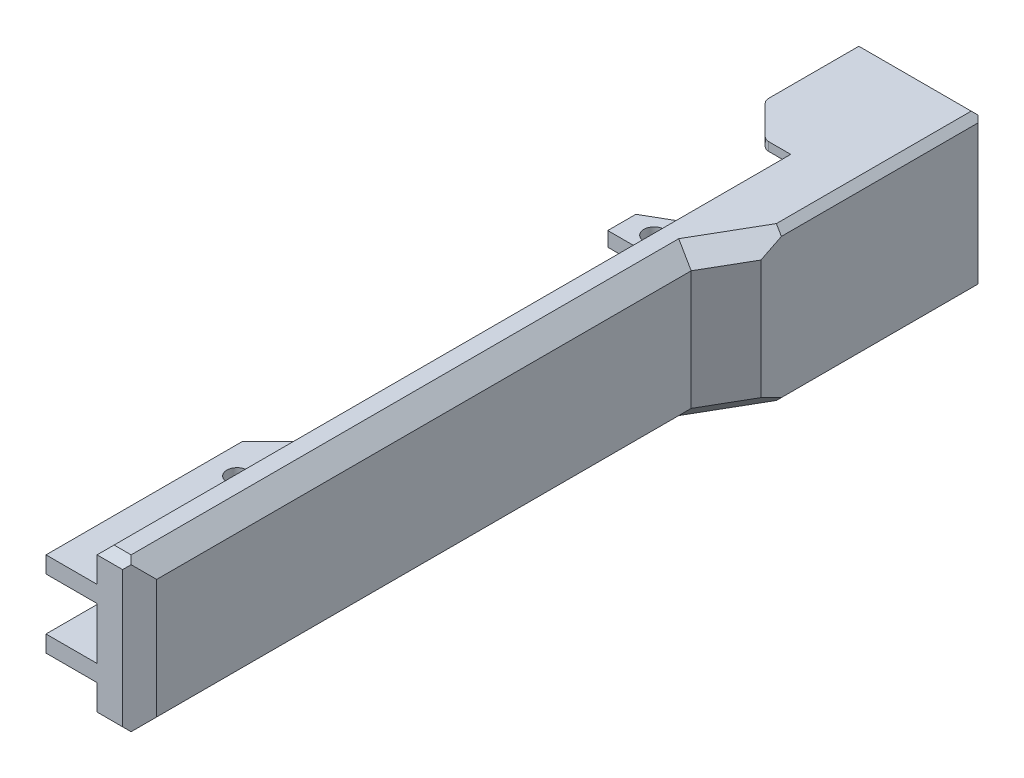
SolidWorks part; units mm, degrees
ref_plane "前视基准面" through (0, 0, 0) normal (0, 0, 1) x (1, 0, 0)
ref_plane "上视基准面" through (0, 0, 0) normal (0, 1, 0) x (1, 0, 0)
ref_plane "右视基准面" through (0, 0, 0) normal (1, 0, 0) x (0, 0, -1)
sketch "草图2" plane through (0, 0, 0) normal (1, 0, 0) x (0, 0, -1)
  line L0 (-24.1958, 9) -> (135.844, 9) construction
  line L1 (0, 0) -> (96.5, 0)
  line L2 (0, 0) -> (0, 18)
  line L3 (0, 18) -> (96.5, 18)
  line L4 (96.5, 0) -> (96.5, 18)
  dimension "D1" = 18
  dimension "D2" = 96.5
extrude "凸台-拉伸1" add sketch "草图2" along normal blind 14
sketch "草图6" plane through (0, 0, -96.5) normal (0, 0, -1) x (-1, 0, 0)
  line L0 (0, 0) -> (0, 18) construction
  line L1 (0, 12.05) -> (-6, 12.05)
  line L2 (0, 12.05) -> (0, 5.95)
  line L3 (0, 5.95) -> (-6, 5.95)
  line L4 (-6, 12.05) -> (-6, 5.95)
  line L5 (5.6103, 9) -> (-10.6258, 9) construction
  line L6 (0, 18) -> (-6, 18)
  line L7 (0, 18) -> (0, 14)
  line L8 (0, 14) -> (-6, 14)
  line L9 (-6, 18) -> (-6, 14)
  line L10 (0, 0) -> (-6, 0)
  line L11 (0, 0) -> (0, 4)
  line L12 (0, 4) -> (-6, 4)
  line L13 (-6, 0) -> (-6, 4)
  line M13 (0, 0) -> (0, 18)
  line M14 (0, 18) -> (-14, 18)
  line M16 (-14, 0) -> (0, 0)
  dimension "D1" = 6.1
  dimension "D2" = 6
  dimension "D3" = 4
extrude "切除-拉伸3" cut sketch "草图6" against normal through all contours L9 L8 M14 M13 | L13 L12 M16 M13 region at (3, 2, -96.5) region at (3, 16, -96.5)
extrude "切除-拉伸5" cut sketch "草图6<4>" against normal through all from offset 4 contours L3 L4 L1 L2 offset against normal yes
sketch "草图6<4>" plane through (0, 0, -96.5) normal (0, 0, -1) x (-1, 0, 0) same geometry as "草图6"
sketch "草图7" plane through (0, 0, 0) normal (-1, 0, 0) x (0, 0, 1)
  line L0 (-88.9, 14) -> (-7.6, 14) construction
  line L1 (-96.5, 14) -> (-23.1, 14)
  line L2 (-96.5, 14) -> (-96.5, 4)
  line L3 (-96.5, 4) -> (-23.1, 4)
  line L4 (-23.1, 14) -> (-23.1, 4)
  line L5 (-7.6, 4) -> (-88.9, 4) construction
  line L6 (-96.5, 4) -> (-96.5, 14) construction
  line L8 (0, 14) -> (0, 12.05) construction
  dimension "D1" = 23.1
  dimension "D2" = 0
extrude "切除-拉伸4" cut sketch "草图7" against normal up to surface (6 mm away) up to face at (6, 16, -48.25)
sketch "草图8" plane through (0, 14, 0) normal (0, 1, 0) x (1, 0, 0)
  circle A0 centre (3.2, 19.25) radius 1.2 construction
  circle A1 centre (3.2, 19.25) radius 1.2
extrude "切除-拉伸6" cut sketch "草图8" against normal through all
sketch "草图10" plane through (6, 0, 0) normal (-1, 0, 0) x (0, 0, 1)
  line L0 (0, 18) -> (-96.5, 18) construction
  line L1 (-96.5, 0) -> (-94.5, 0)
  line L2 (-96.5, 0) -> (-96.5, 18)
  line L3 (-96.5, 18) -> (-94.5, 18)
  line L4 (-94.5, 0) -> (-94.5, 18)
  dimension "D1" = 2
extrude "凸台-拉伸3" add sketch "草图10" along normal blind 6
sketch "草图11" plane through (6, 0, 0) normal (-1, 0, 0) x (0, 0, 1)
  line L0 (-94.5, 0) -> (-94.5, 18) construction
  line L1 (-94.5, 3) -> (-92.5, 3)
  line L2 (-94.5, 3) -> (-94.5, 15)
  line L3 (-94.5, 15) -> (-92.5, 15)
  line L5 (-106.5209, 9) -> (-53.1041, 9) construction
  line L6 (-92.5, 1) -> (-74.5, 1)
  line L7 (-92.5, 1) -> (-92.5, 3)
  line L8 (-92.5, 17) -> (-74.5, 17)
  line L9 (-74.5, 1) -> (-74.5, 17)
  line L10 (0, 18) -> (-94.5, 18) construction
  line L11 (0, 0) -> (-94.5, 0) construction
  line L12 (-92.5, 15) -> (-92.5, 17)
  dimension "D1" = 12
  dimension "D2" = 16
  dimension "D3" = 2
  dimension "D4" = 18
extrude "切除-拉伸7" cut sketch "草图11" against normal offset from surface (7 mm away) 1 up to face at (14, 9, -48.25)
chamfer "倒角4" distance 1 angle 45 5 edges at (7, 0, -96.5) (14, 9, -96.5) (7, 18, -96.5) (6, 0, -47.25) (6, 18, -47.25)
sketch "草图12" plane through (0, 0, -96.5) normal (0, 0, -1) x (-1, 0, 0)
  line L0 (0, 0) -> (-14, 0) construction
  line L1 (-14, 18) -> (0, 18) construction
  line L2 (0, 0) -> (-14, 0) construction
  line L3 (-14, 18) -> (0, 18) construction
  line L4 (-19.9188, 9) -> (6.984, 9) construction
  line L5 (0, 17) -> (0, 1) construction
  circle A0 centre (-7, 9) radius 3.55
  dimension "D1" = 7
  dimension "D2" = 7.1
extrude "切除-拉伸8" cut sketch "草图12" against normal blind 5
chamfer "倒角6" distance 0.8 angle 45 2 edges at (14, 0, -47.75) (14, 18, -47.75)
chamfer "倒角7" distance 1 angle 45 2 edges at (10.1, 0, 0) (10.1, 18, 0)
sketch "草图13" plane through (14, 0, 0) normal (1, 0, 0) x (0, 0, -1)
  line L0 (1, 18) -> (95.5, 18) construction
  line L1 (94.5, 0) -> (80.5, 0)
  line L2 (94.5, 0) -> (94.5, 1)
  line L3 (94.5, 18) -> (80.5, 18)
  line L4 (80.5, 0) -> (80.5, 1)
  line L5 (95.5, 0) -> (1, 0) construction
  line L7 (94.5, 3) -> (94.5, 15) construction
  line L10 (80.5, 1) -> (94.5, 1)
  line L11 (94.5, 17) -> (80.5, 17)
  line L12 (80.5, 17) -> (80.5, 18)
  line L13 (94.5, 17) -> (94.5, 18)
  line L14 (74.5, 1) -> (92.5, 1) construction
  dimension "D1" = 0
  dimension "D2" = 14
  dimension "D3" = 1
  dimension "D4" = 1
extrude "凸台-拉伸4" add sketch "草图13" against normal up to surface (14 mm away) from offset 5 up to face at (0, 9, -95.5) offset against normal yes
chamfer "倒角8" distance 6 angle 45 2 edges at (6, 4.975, -23.1) (6, 13.025, -23.1)
chamfer "倒角9" distance 4 angle 45 2 edges at (0, 17.5, -80.5) (0, 0.5, -80.5)
chamfer "倒角10" distance 3 angle 30 1 edges at (6, 9, -74.5) first distance on face at (9.5, 9, -74.5)
sketch "草图14" plane through (6, 0, 0) normal (-1, 0, 0) x (0, 0, 1)
  line L1 (-74.5, 6) -> (-39.5, 6)
  line L2 (-74.5, 6) -> (-74.5, 12)
  line L3 (-74.5, 12) -> (-39.5, 12)
  line L4 (-39.5, 6) -> (-39.5, 12)
  line L6 (-76.9979, 9) -> (-20.6366, 9) construction
  line L7 (0, 17) -> (-72.7679, 17) construction
  line L8 (-72.7679, 1) -> (0, 1) construction
  line L9 (-74.5, 1) -> (-74.5, 17) construction
  dimension "D1" = 6
  dimension "D2" = 35
extrude "切除-拉伸9" cut sketch "草图14" against normal blind 2
chamfer "倒角11" distance 4 angle 45 1 edges at (13, 9, -74.5)
ref_plane "基准面1" through (0, 9, 0) normal (0, -1, 0) x (-1, 0, 0)
sketch "草图15" plane through (0, 0, 0) normal (0, -1, 0) x (1, 0, 0)
  line L0 (6, 0) -> (14, 0) construction
  line L1 (6, 0) -> (14, 0) construction
  line L3 (14, 0) -> (11, 0)
  line L4 (14, 0) -> (14, -70)
  line L5 (14, -70) -> (11, -70)
  line L6 (11, 0) -> (11, -70)
  dimension "D1" = 3
  dimension "D2" = 70
extrude "切除-拉伸10" cut sketch "草图15" against normal through all
chamfer "倒角12" distance 3 angle 60 1 edges at (11, 9, -70) first distance on face at (12.7333, 9, -70)
chamfer "倒角13" distance 2 angle 45 7 edges at (12.1, 0, -66.7091) (11, 0, -32.9019) (11, 0.5, -0.5) (11, 9, 0) (11, 17.5, -0.5) (12.1, 18, -66.7091) (11, 18, -32.9019)
chamfer "倒角14" distance 2 angle 45 1 edges at (6, 9, -39.5)
sketch "草图16" plane through (0, 17, 0) normal (0, -1, 0) x (1, 0, 0)
  line L1 (6, -80.5) -> (7, -80.5)
  line L2 (6, -80.5) -> (6, -68.5)
  line L3 (6, -68.5) -> (7, -68.5)
  line L4 (7, -80.5) -> (7, -68.5)
  dimension "D1" = 12
  dimension "D2" = 1
extrude "凸台-拉伸5" add sketch "草图16" along normal blind 0.8
extrude "凸台-拉伸6" add sketch "草图16<2>" against normal blind 0.8 from surface starting at face at (6.3, 1, -84.5268)
sketch "草图16<2>" plane through (0, 17, 0) normal (0, -1, 0) x (1, 0, 0) same geometry as "草图16"
chamfer "倒角15" distance 0.8 angle 45 4 edges at (7, 17, -76.9226) (6.5, 17, -80.5) (6.5, 1, -80.5) (7, 1, -76.9226)
fillet "圆角1" radius 1 4 edges at (0, 17.5, -84.5) (4, 17.5, -80.5) (4, 0.5, -80.5) (0, 0.5, -84.5)
sketch "草图17" plane through (0, 6, 0) normal (0, 1, 0) x (1, 0, 0)
  line L0 (6, 72.7679) -> (6, 66)
  line L1 (6, 72.7679) -> (6, 37.5) construction
  line L2 (6, 66) -> (0, 66)
  line L3 (0, 66) -> (0, 69.3038)
  line L4 (0, 69.3038) -> (6, 72.7679)
  line L5 (8, 73.9226) -> (6, 72.7679) construction
  line L6 (0, 0) -> (6, 0) construction
  dimension "D1" = 66
  dimension "D2" = 6
extrude "凸台-拉伸7" add sketch "草图17" against normal blind 2
extrude "凸台-拉伸8" add sketch "草图17<2>" along normal blind 2 from surface starting at face at (7, 12, -55.9226)
sketch "草图17<2>" plane through (0, 6, 0) normal (0, 1, 0) x (1, 0, 0) same geometry as "草图17"
sketch "草图18" plane through (0, 14, 0) normal (0, 1, 0) x (1, 0, 0)
  circle A0 centre (3.2, 68.25) radius 1.2 construction
  circle A1 centre (3.2, 68.25) radius 1.2
extrude "切除-拉伸11" cut sketch "草图18" against normal through all
chamfer "倒角16" distance 0.3 angle 45 4 edges at (4, 12, -71.6132) (3, 12, -66) (4, 6, -71.6132) (3, 6, -66)
